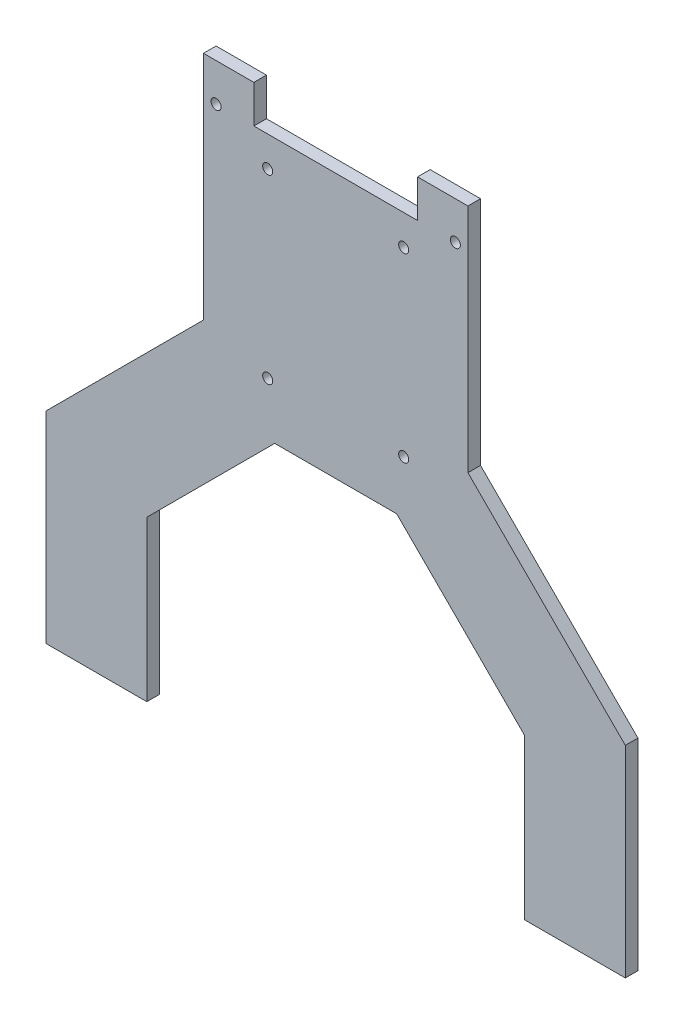
SolidWorks part; units mm, degrees
ref_plane "Front Plane" through (0, 0, 0) normal (0, 0, 1) x (1, 0, 0)
ref_plane "Top Plane" through (0, 0, 0) normal (0, 1, 0) x (1, 0, 0)
ref_plane "Right Plane" through (0, 0, 0) normal (1, 0, 0) x (0, 0, -1)
sketch "Sketch1" plane through (0, 0, 0) normal (0, 0, 1) x (1, 0, 0)
  line L1 (-100, -75) -> (100, -75)
  line L2 (-100, -75) -> (-100, 75)
  line L3 (-100, 75) -> (100, 75)
  line L4 (100, -75) -> (100, 75)
  line L5 (-100, -75) -> (100, 75) construction
  line L6 (-100, 75) -> (100, -75) construction
  line L8 (-47.5, 45) -> (47.5, 45) construction
  line L9 (0, 75) -> (0, -75) construction
  line L10 (-27, -39) -> (27, -39) construction
  line L11 (-27, -39) -> (-27, 33) construction
  line L12 (-27, 33) -> (27, 33) construction
  line L13 (27, -39) -> (27, 33) construction
  line L14 (-27, -39) -> (27, 33) construction
  line L15 (-27, 33) -> (27, -39) construction
  line L23 (-52.5, 60) -> (52.5, 60)
  line L24 (-52.5, 60) -> (-52.5, -60)
  line L25 (-52.5, -60) -> (52.5, -60)
  line L26 (52.5, 60) -> (52.5, -60)
  line L27 (-52.5, 60) -> (52.5, -60) construction
  line L28 (-52.5, -60) -> (52.5, 60) construction
  line L29 (-32.5, 60) -> (32.5, 60)
  line L30 (-32.5, 60) -> (-32.5, 45)
  line L31 (-32.5, 45) -> (32.5, 45)
  line L32 (32.5, 60) -> (32.5, 45)
  line L33 (-32.5, 60) -> (32.5, 45) construction
  line L34 (-32.5, 45) -> (32.5, 60) construction
  circle A2 centre (-47.5, 45) radius 2
  circle A3 centre (47.5, 45) radius 2
  circle A4 centre (-27, 33) radius 2
  circle A5 centre (27, 33) radius 2
  circle A6 centre (27, -39) radius 2
  circle A7 centre (-27, -39) radius 2
  point P0 (0, 0)
  point P6 (0, 0)
  point P15 (0, 45)
  point P18 (0, -3)
  point P56 (0, 0)
  point P63 (0, 52.5)
  dimension "D5" = 4
  dimension "D8" = 4
  dimension "D1" = 150
  dimension "D2" = 200
  dimension "D6" = 72
  dimension "D7" = 54
  dimension "D14" = 15
  dimension "D15" = 120
  dimension "D16" = 105
  dimension "D17" = 95
  dimension "D18" = 12
  dimension "D19" = 15
  dimension "D20" = 65
extrude "Boss-Extrude1" add sketch "Sketch1" along normal blind 5 contours L23 L32 L31 L30 L24 L25 L26 A7 A6 A5 A4 A3 A2 region at (0, -4.5168, 0)
sketch "Sketch2" plane through (0, 0, 0) normal (0, 0, 1) x (1, 0, 0)
  line L0 (-52.5, -60) -> (-100.8579, -108.3579) construction
  line L1 (-52.5, 60) -> (-52.5, -60) construction
  line L2 (-52.5, -31.7157) -> (-115, -94.2157)
  line L3 (-24.2157, -60) -> (-86.7157, -122.5)
  line L4 (-52.5, -60) -> (52.5, -60) construction
  line L5 (-115, -94.2157) -> (-86.7157, -122.5)
  line L6 (-115, -94.2157) -> (-115, -174.2157)
  line L7 (-75, -110.7843) -> (-75, -174.2157)
  line L8 (-75, -174.2157) -> (-115, -174.2157)
  line L9 (0, 75) -> (0, -75) construction
  line L10 (-52.5, -31.7157) -> (-24.2157, -60)
  line L11 (-52.5, 60) -> (-52.5, -60) construction
  point P16 (-100, -89.8223)
  point P17 (-52.5, -42.3223)
  point P20 (-75, -110.7843)
  point P21 (-75, -110.7843)
  dimension "D1" = 135
  dimension "D2" = 40
  dimension "D3" = 40
  dimension "D4" = 75
  dimension "D5" = 80
extrude "Boss-Extrude2" add sketch "Sketch2" along normal blind 5 contours L8 L7 L3 L5 L6 | L10 L2 L5 L3 region at (-69.6079, -77.1079, 0) region at (-96.2313, -141.99, 0)
mirror "Mirror1" about plane through (0, 0, 0) normal (1, 0, 0) of "Boss-Extrude2"
